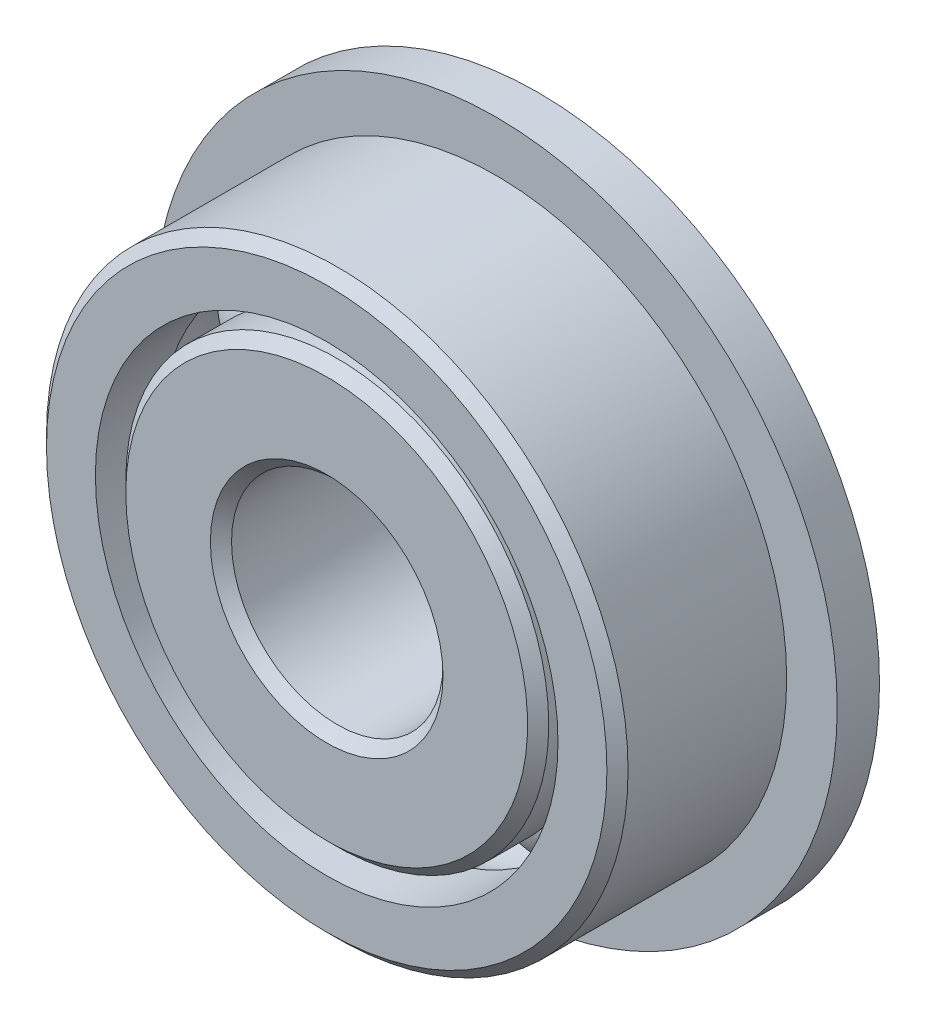
SolidWorks part; units mm, degrees
ref_plane "Front Plane" through (0, 0, 0) normal (0, 0, 1) x (1, 0, 0)
ref_plane "Top Plane" through (0, 0, 0) normal (0, 1, 0) x (1, 0, 0)
ref_plane "Right Plane" through (0, 0, 0) normal (1, 0, 0) x (0, 0, -1)
sketch "Sketch1" plane through (0, 0, 0) normal (1, 0, 0) x (0, 0, -1)
  line L0 (-3.175, 0) -> (3.175, 0) construction
  line L1 (0, 8.7312) -> (0, -8.7312) construction
  line L2 (2.8575, 8.7312) -> (-2.8575, 8.7312)
  line L3 (-2.8575, 8.7312) -> (-3.175, 8.4138)
  line L4 (-3.175, 8.4138) -> (-3.175, 6.9453)
  line L5 (-3.175, 6.9453) -> (-1.2392, 6.9453)
  line L6 (3.175, 6.9453) -> (1.2392, 6.9453)
  line L7 (3.175, 8.4138) -> (3.175, 6.9453)
  line L8 (2.8575, 8.7312) -> (3.175, 8.4138)
  line L9 (0, 8.7312) -> (0, 5.9531) construction
  line L10 (0, 5.9531) -> (0, 3.175) construction
  line L11 (3.175, 6.35) -> (3.175, -6.35) construction
  line L12 (-3.175, 3.175) -> (3.175, 3.175) construction
  line L13 (0, 4.3656) -> (0, 3.175) construction
  line L14 (0, 7.5406) -> (0, 8.7312) construction
  line L15 (3.175, 6.35) -> (0, 6.35) construction
  circle A1 centre (0, 5.9531) radius 1.5875 construction
  arc A2 (-1.2392, 6.9453) -> (1.2392, 6.9453) centre (0, 5.9531) cw
  point P14 (0, 3.175)
  point P22 (0, 4.3656)
  point P23 (0, 7.5406)
  dimension "D3" = 3.175
  dimension "Width" = 6.35
  dimension "OD" = 17.4625
  dimension "D1" = 45
  dimension "D2" = 0.3175
  dimension "D4" = 12.7
  dimension "D5" = 1.1906
  dimension "D6" = 0.5953
revolve "Revolve1" add sketch "Sketch1" angle 360 about L0
sketch "Sketch3" plane through (0, 0, 0) normal (1, 0, 0) x (0, 0, -1)
  line L1 (-3.175, 8.4138) -> (-3.175, 6.9453) construction
  line L2 (-2.8575, 8.7312) -> (-3.175, 8.4138) construction
  line L3 (-3.175, 4.9609) -> (-3.175, 3.4925) construction
  line L4 (-3.175, 3.4925) -> (-3.175, 6.0325)
  line L5 (-3.175, 3.4925) -> (-2.8575, 3.175)
  line L6 (-2.8575, 3.175) -> (4.4577, 3.175)
  line L7 (-3.175, 8.4138) -> (-3.175, -8.4138) construction
  line L8 (4.4577, 3.175) -> (4.7752, 3.4925)
  line L9 (0, 0) -> (4.7752, 0) construction
  line L13 (2.8575, 8.7312) -> (3.175, 8.4138) construction
  line L14 (-3.175, 6.0325) -> (-2.8575, 6.35)
  line L15 (-2.8575, 6.35) -> (-1.5371, 6.35)
  line L16 (1.5371, 6.35) -> (4.4577, 6.35)
  line L17 (4.4577, 6.35) -> (4.7752, 6.0325)
  line L18 (4.7752, 6.0325) -> (4.7752, 3.4925)
  circle A0 centre (0, 5.9531) radius 1.5875 construction
  arc A1 (-1.5371, 6.35) -> (1.5371, 6.35) centre (0, 5.9531) ccw
  dimension "D1" = 45
  dimension "Ring Wd" = 7.9502
  dimension "Inner Ring OD" = 12.7
revolve "Revolve3" add sketch "Sketch3" angle 360 about L0
sketch "Sketch6" plane through (0, 0, 0) normal (1, 0, 0) x (0, 0, -1)
  line L1 (3.175, 6.9453) -> (1.905, 6.9453)
  line L2 (3.175, 6.9453) -> (3.175, 10.2489)
  line L3 (3.175, 10.2489) -> (1.905, 10.2489)
  line L4 (1.905, 6.9453) -> (1.905, 10.2489)
  line L5 (3.175, 0) -> (-3.175, 0) construction
  dimension "Flange OD" = 20.4978
  dimension "Flange Thickness" = 1.27
revolve "Revolve6" add sketch "Sketch6" angle 360 about L5
sketch "Sketch4" plane through (0, 0, 0) normal (1, 0, 0) x (0, 0, -1)
  line L0 (-1.5875, 5.9531) -> (1.5875, 5.9531)
  circle A0 centre (0, 5.9531) radius 1.5875 construction
  arc A1 (1.5875, 5.9531) -> (-1.5875, 5.9531) centre (0, 5.9531) ccw
revolve "Revolve4" add sketch "Sketch4" angle 360 about L0
ref_axis "Axis1" through (0, 0, -3.175) along (0, 0, 1)
pattern_circular "CirPattern1" count 8 every 45 about axis through (0, 0, -3.175) along (0, 0, 1) of bodies 104
sketch "Sketch5" plane through (0, 0, 0) normal (1, 0, 0) x (0, 0, -1)
  line L0 (-3.175, 6.9453) -> (-1.2392, 6.9453) construction
  line L1 (-3.0162, 6.9453) -> (-1.5371, 6.9453)
  line L2 (-3.0162, 6.9453) -> (-3.0162, 6.35)
  line L3 (-3.0162, 6.35) -> (-1.5371, 6.35)
  line L4 (-1.5371, 6.9453) -> (-1.5371, 6.35)
  line L6 (3.175, 6.9453) -> (1.2392, 6.9453) construction
  line L7 (3.0163, 6.9453) -> (1.5371, 6.9453)
  line L8 (3.0163, 6.9453) -> (3.0163, 6.35)
  line L9 (3.0163, 6.35) -> (1.5371, 6.35)
  line L10 (1.5371, 6.9453) -> (1.5371, 6.35)
  line L12 (-2.8575, 8.7312) -> (-3.175, 8.4138) construction
  line L13 (3.175, 6.35) -> (0, 6.35) construction
  line L15 (-2.8575, 6.35) -> (-1.5371, 6.35) construction
  line L16 (3.0163, 6.9453) -> (3.0163, 8.5725) construction
  line L17 (2.8575, 8.7312) -> (3.175, 8.4138) construction
  point P18 (-3.0162, 8.5725)
revolve "Revolve5" [suppressed] add sketch "Sketch5" angle 360 about L0
equation "\"D2@Sketch1\" = \"Width@Sketch1\"*.05"
equation "\"D2@CirPattern1\" = 360/\"Balls@CirPattern1\""
equation "\"D4@Sketch1\"=\"Inner Ring OD@Sketch3\""
equation "\"D3@Sketch1\"=\"Width@Sketch1\"/2"
equation "\"D6@Sketch1\"=\"D5@Sketch1\"/2"
